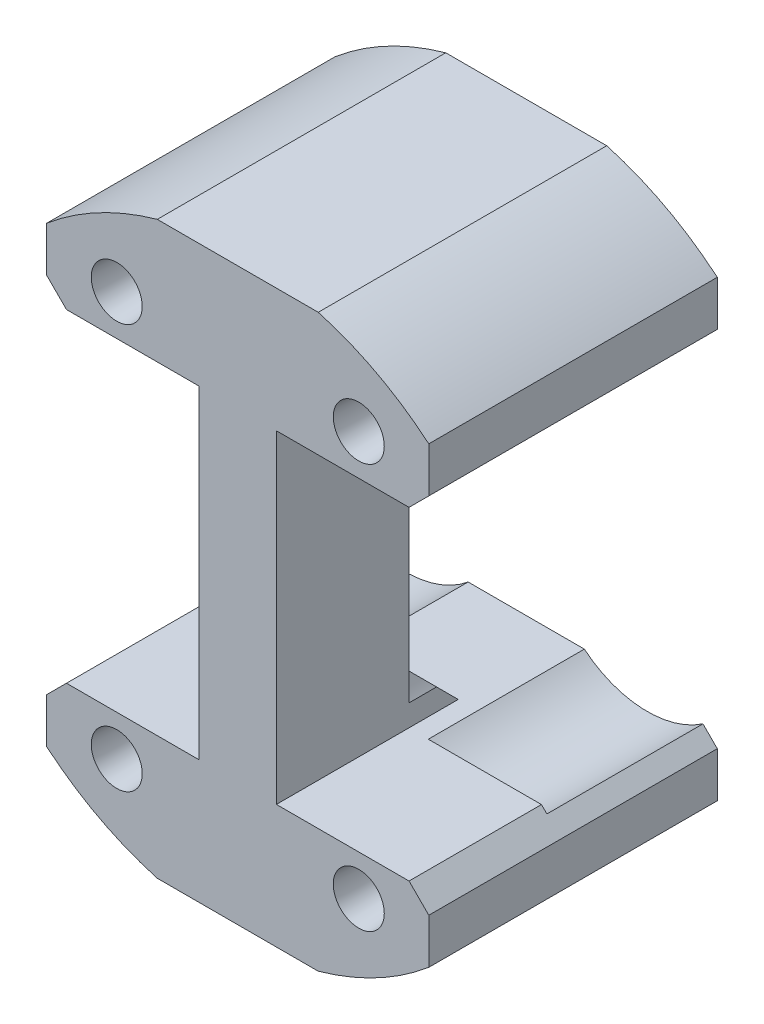
SolidWorks part; units mm, degrees
material "PET"
ref_plane "Front Plane" through (0, 0, 0) normal (0, 0, 1) x (1, 0, 0)
ref_plane "Top Plane" through (0, 0, 0) normal (0, 1, 0) x (1, 0, 0)
ref_plane "Right Plane" through (0, 0, 0) normal (1, 0, 0) x (0, 0, -1)
sketch "Sketch1" plane through (0, 0, 0) normal (0, 0, 1) x (1, 0, 0)
  line L0 (-3.2766, -10) -> (-12.2766, -10) construction
  line L1 (-12.2766, -10.3969) -> (12.2766, -10.3969)
  line L2 (-12.2766, -10.3969) -> (-12.2766, -18.3344)
  line L3 (-12.2766, -18.3344) -> (12.2766, -18.3344)
  line L4 (12.2766, -10.3969) -> (12.2766, -18.3344)
  line L6 (-12.2766, -10) -> (-12.2766, -12.5) construction
  line L8 (12.2766, -12.5) -> (12.2766, -10) construction
  dimension "D1" = 0.3969
  dimension "D2" = 7.9375
extrude "Boss-Extrude1" add sketch "Sketch1" along normal up to surface (18.5375 mm away)
sketch "Sketch8" plane through (0, 0, 0) normal (0, 0, -1) x (-1, 0, 0)
  line L0 (5.1723, -18.3344) -> (12.2766, -18.3344)
  line L4 (12.2766, -18.3344) -> (12.2766, -10.3969)
  line L5 (12.2766, -10.3969) -> (-12.2766, -10.3969)
  line L6 (-12.2766, -10.3969) -> (-12.2766, -18.3344)
  line L7 (-12.2766, -18.3344) -> (12.2766, -18.3344)
  line L8 (12.2766, -18.3344) -> (12.2766, -14.5667)
  line L10 (-12.2766, -14.5667) -> (-12.2766, -18.3344)
  line L11 (-12.2766, -18.3344) -> (-5.1723, -18.3344)
  arc A0 (-17.3537, -7.8581) -> (17.3537, -7.8581) centre (0, 0) ccw construction
  arc A1 (-12.2766, -14.5667) -> (-5.1723, -18.3344) centre (0, 0) ccw
  arc A2 (5.1723, -18.3344) -> (12.2766, -14.5667) centre (0, 0) ccw
  dimension "D1" = 0
extrude "Cut-Extrude2" cut sketch "Sketch8" against normal through all
ref_plane "Plane1" through (0, 0, 0) normal (0, -1, 0) x (-1, 0, 0)
mirror "Mirror2" about plane through (0, 0, 0) normal (0, -1, 0) of bodies 106 102
sketch "Sketch3" plane through (0, 0, 18.5375) normal (0, 0, 1) x (1, 0, 0)
  line L0 (0, 10.3969) -> (0, -10.3969) construction
  line L1 (-12.2766, 10.3969) -> (12.2766, 10.3969) construction
  line L2 (-12.2766, -10.3969) -> (12.2766, -10.3969) construction
  line L3 (-3.2766, 10) -> (-3.2766, -10) construction
  line L4 (2.4829, -10.3969) -> (-2.4829, -10.3969)
  line L5 (2.4829, -10.3969) -> (2.4829, 10.3969)
  line L6 (2.4829, 10.3969) -> (-2.4829, 10.3969)
  line L7 (-2.4829, -10.3969) -> (-2.4829, 10.3969)
  line L8 (2.4829, -10.3969) -> (-2.4829, 10.3969) construction
  line L9 (2.4829, 10.3969) -> (-2.4829, -10.3969) construction
  point P6 (0, 0)
  dimension "D1" = 0.7937
extrude "Boss-Extrude2" add sketch "Sketch3" against normal blind 8.509
chamfer "Chamfer2" distance 3.175 angle 45 2 edges at (0, 10.3969, 10.0285) (0, -10.3969, 10.0285)
chamfer "Chamfer4" distance 1.27 angle 45 4 edges at (-12.2766, -10.3969, 9.2688) (-12.2766, 10.3969, 9.2688) (12.2766, 10.3969, 9.2688) (12.2766, -10.3969, 9.2688)
sketch "Sketch2" plane through (0, 0, 0) normal (0, 0, -1) x (-1, 0, 0)
  line L0 (-28.4114, 0) -> (28.4114, 0) construction
  arc A0 (4.6029, 0) -> (10.9503, 0) centre (7.7766, -5.5) ccw
  arc A1 (-10.9503, 0) -> (-4.6029, 0) centre (-7.7766, -5.5) ccw
  arc A2 (4.6029, 0) -> (10.9503, 0) centre (7.7766, 5.5) cw
  arc A3 (-10.9503, 0) -> (-4.6029, 0) centre (-7.7766, 5.5) cw
  circle A4 centre (7.7766, -5.5) radius 3.175 construction
  point P1 (0, 0)
  point P9 (0, 0)
  dimension "D1" = 12.7
extrude "Cut-Extrude1" cut sketch "Sketch2" against normal up to surface (10.0285 mm away) up to face at (0, 0, 10.0285)
hole_wizard "Hole1" positions "Sketch4" profile "Sketch5" legacy
sketch "Sketch4" plane through (0, 0, 18.5375) normal (0, 0, 1) x (1, 0, 0)
  point P0 (-7.7766, 13)
  point P3 (7.7766, 13)
  point P6 (7.7766, -13)
  point P9 (-7.7766, -13)
sketch "Sketch5" plane through (-7.7766, 13, 18.5375) normal (1, 0, 0) x (0, -1, 0)
  line L0 (0, 0) -> (0, 2.921)
  line L1 (0, 2.921) -> (1.4986, 2.921)
  line L2 (1.4986, 2.921) -> (1.6383, 0)
  line L3 (1.6383, 0) -> (0, 0)
  line L4 (0, 110) -> (0, -10) construction
  dimension "Minor Diameter" = 2.9972
  dimension "Depth" = 2.921
  dimension "Major Diameter" = 3.2766
hole_wizard "#0 Clearance Hole1" positions "Sketch10" profile "Sketch11" hole size "#0" standard "ANSI Inch"
sketch "Sketch10" plane through (0, 0, 18.5375) normal (0, 0, 1) x (1, 0, 0)
  point P0 (7.7766, 13)
  point P3 (7.7766, -13)
  point P6 (-7.7766, -13)
  point P9 (-7.7766, 13)
sketch "Sketch11" plane through (7.7766, 13, 18.5375) normal (1, 0, 0) x (0, -1, 0)
  line L0 (0, 0) -> (0, 6.9071)
  line L1 (0, 6.9071) -> (0.9271, 6.35)
  line L2 (0.9271, 6.35) -> (0.9271, 0)
  line L5 (0.9271, 0) -> (0, 0)
  line L10 (0, 6.9071) -> (-0.9271, 6.35) construction
  line L11 (0, -6.35) -> (0, 107.95) construction
  dimension "Hole Dia." = 1.8542
  dimension "Hole Depth" = 6.35
  dimension "Drill Angle" = 118
hole_wizard "Hole2" positions "3DSketch1" profile "Sketch9" legacy
sketch3d "3DSketch1"
  line L0 (7.435, -11.8408, 0) -> (7.435, -17.5392, 0) construction
  line L2 (-7.7474, -11.8499, 0) -> (-7.7474, -17.4034, 0) construction
  line L4 (0, 0, 0) -> (-12.2766, 0, 0) construction
  line L6 (-12.2766, 11.6669, 0) -> (-12.2766, 14.5667, 0) construction
  line L7 (7.435, 11.8408, 0) -> (7.435, 17.5392, 0) construction
  line L9 (-7.7474, 11.8499, 0) -> (-7.7474, 17.4034, 0) construction
  arc A0 (11.3553, -10.7455, 0) -> (3.7339, -10.3969, 0) centre (7.7766, -5.5, 0) ccw construction
  arc A1 (5.1723, -18.3344, 0) -> (12.2766, -14.5667, 0) centre (0, 0, 0) ccw construction
  arc A2 (-3.7339, -10.3969, 0) -> (-11.3553, -10.7455, 0) centre (-7.7766, -5.5, 0) ccw construction
  arc A3 (-12.2766, -14.5667, 0) -> (-5.1723, -18.3344, 0) centre (0, 0, 0) ccw construction
  arc A4 (3.7339, 10.3969, 0) -> (11.3553, 10.7455, 0) centre (7.7766, 5.5, 0) ccw construction
  arc A5 (5.1723, 18.3344, 0) -> (12.2766, 14.5667, 0) centre (0, 0, 0) ccw construction
  arc A6 (-11.3553, 10.7455, 0) -> (-3.7339, 10.3969, 0) centre (-7.7766, 5.5, 0) ccw construction
  arc A7 (-12.2766, 14.5667, 0) -> (-5.1723, 18.3344, 0) centre (0, 0, 0) ccw construction
  point P4 (7.435, -14.69, 0)
  point P6 (-7.7474, -14.6946, 0)
  point P15 (7.7766, -5.5, -6.35)
  point P19 (0, 0, 19.05)
  point P27 (-7.7766, -5.5, -6.35)
  point P31 (0, 0, 19.05)
  point P44 (7.435, 14.69, 0)
  point P46 (-7.7474, 14.6946, 0)
  point P54 (7.7766, 5.5, -6.35)
  point P58 (0, 0, -19.05)
  point P65 (-7.7766, 5.5, -6.35)
  point P69 (0, 0, -19.05)
  point P71 (7.435, 13.296, 0)
  point P72 (7.435, 14.69, 0)
  point P73 (-7.7474, 14.6946, 0)
  point P74 (0, 0, 0)
  point P75 (7.435, -14.69, 0)
  point P76 (-7.7474, -14.6946, 0)
sketch "Sketch9" plane through (7.435, -14.69, 0) normal (1, 0, 0) x (0, 1, 0)
  line L0 (0, 0) -> (0, 2.921)
  line L1 (0, 2.921) -> (1.4986, 2.921)
  line L2 (1.4986, 2.921) -> (1.6383, 0)
  line L3 (1.6383, 0) -> (0, 0)
  line L4 (0, 110) -> (0, -10) construction
  dimension "Minor Diameter" = 2.9972
  dimension "Depth" = 2.921
  dimension "Major Diameter" = 3.2766
hole_wizard "#0 Clearance Hole2" positions "Sketch12" profile "Sketch13" hole size "#0" standard "ANSI Inch"
sketch "Sketch12" plane through (0, 0, 0) normal (0, 0, -1) x (-1, 0, 0)
  point P0 (-7.435, -14.69)
  point P3 (-7.435, 14.69)
  point P6 (7.7474, 14.6946)
  point P9 (7.7474, -14.6946)
sketch "Sketch13" plane through (7.435, -14.69, 0) normal (1, 0, 0) x (0, 1, 0)
  line L0 (0, 0) -> (0, 6.9071)
  line L1 (0, 6.9071) -> (0.9271, 6.35)
  line L2 (0.9271, 6.35) -> (0.9271, 0)
  line L5 (0.9271, 0) -> (0, 0)
  line L10 (0, 6.9071) -> (-0.9271, 6.35) construction
  line L11 (0, -6.35) -> (0, 107.95) construction
  dimension "Hole Dia." = 1.8542
  dimension "Hole Depth" = 6.35
  dimension "Drill Angle" = 118
